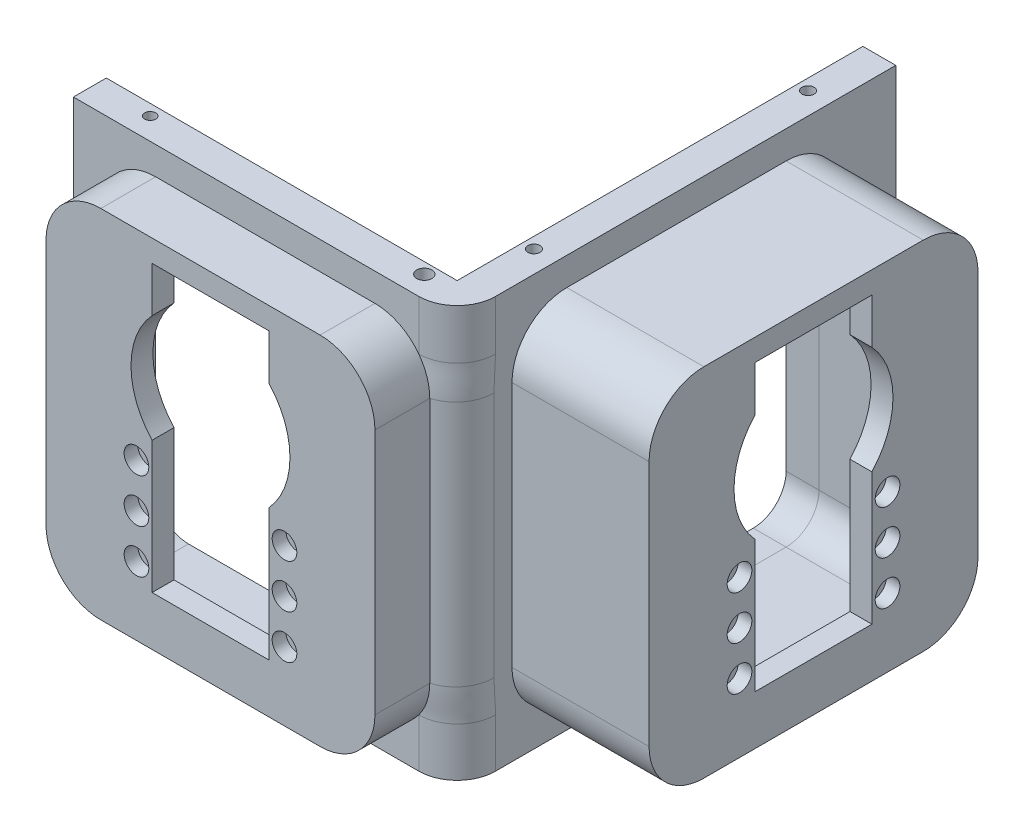
SolidWorks part; units mm, degrees
ref_plane "Front Plane" through (0, 0, 0) normal (0, 0, 1) x (1, 0, 0)
ref_plane "Top Plane" through (0, 0, 0) normal (0, 1, 0) x (1, 0, 0)
ref_plane "Right Plane" through (0, 0, 0) normal (1, 0, 0) x (0, 0, -1)
sketch "Sketch1" plane through (0, 0, 0) normal (0, 0, 1) x (1, 0, 0)
  line L1 (-20, -32.5) -> (20, -32.5)
  line L2 (-30, -22.5) -> (-30, 22.5)
  line L3 (-20, 32.5) -> (20, 32.5)
  line L4 (30, -22.5) -> (30, 22.5)
  line L5 (-30, -32.5) -> (30, 32.5) construction
  line L6 (-30, 32.5) -> (30, -32.5) construction
  arc A1 (20, 32.5) -> (30, 22.5) centre (20, 22.5) cw
  arc A2 (20, -32.5) -> (30, -22.5) centre (20, -22.5) ccw
  arc A3 (-20, -32.5) -> (-30, -22.5) centre (-20, -22.5) cw
  arc A4 (-30, 22.5) -> (-20, 32.5) centre (-20, 22.5) cw
  point P0 (0, 0)
  dimension "D1" = 60
  dimension "D3" = 10
  dimension "D2" = 65
extrude "Boss-Extrude1" add sketch "Sketch1" against normal blind 10
ref_plane "Plane1" through (60, 0, 0) normal (1, 0, 0) x (0, 0, -1)
ref_plane "Plane2" through (60, 0, 0) normal (1, 0, 0) x (0, 0, -1)
sketch "Sketch10" plane through (0, 0, -10) normal (0, 0, -1) x (-1, 0, 0)
  line L0 (0, 0.1039) -> (0, 0) construction
  line L1 (-35, -37.3961) -> (35, -37.3961)
  line L2 (-35, -37.3961) -> (-35, 37.6039)
  line L3 (-35, 37.6039) -> (35, 37.6039)
  line L4 (35, -37.3961) -> (35, 37.6039)
  line L5 (-35, -37.3961) -> (35, 37.6039) construction
  line L6 (-35, 37.6039) -> (35, -37.3961) construction
  point P0 (0, 0.1039)
  point P5 (0, 0.0519)
  dimension "D1" = 75
  dimension "D2" = 70
extrude "Boss-Extrude6" add sketch "Sketch10" along normal blind 80
sketch "Sketch2" plane through (60, 0, 0) normal (1, 0, 0) x (0, 0, -1)
  line L2 (0, 0) -> (146.6861, 0) construction
  line L3 (50, 0) -> (50, 30) construction
  line L5 (10, 37.6039) -> (10, -37.3961) construction
  line L6 (90, 37.6039) -> (90, -37.3961) construction
  line L7 (30, -32.5) -> (70, -32.5)
  line L8 (20, -22.5) -> (20, 22.5)
  line L9 (30, 32.5) -> (70, 32.5)
  line L10 (80, -22.5) -> (80, 22.5)
  line L11 (20, -32.5) -> (80, 32.5) construction
  line L12 (20, 32.5) -> (80, -32.5) construction
  arc A1 (30, -32.5) -> (20, -22.5) centre (30, -22.5) cw
  arc A2 (70, -32.5) -> (80, -22.5) centre (70, -22.5) ccw
  arc A3 (70, 32.5) -> (80, 22.5) centre (70, 22.5) cw
  arc A4 (20, 22.5) -> (30, 32.5) centre (30, 22.5) cw
  dimension "D1" = 60
  dimension "D3" = 10
  dimension "D2" = 65
extrude "Boss-Extrude2" add sketch "Sketch2" against normal up to surface (25 mm away) separate body up to face at (35, 0.1039, -50)
sketch "Sketch11" plane through (0, 37.6039, 0) normal (0, 1, 0) x (1, 0, 0)
  line L1 (-35, 90) -> (29, 90)
  line L2 (-35, 90) -> (-35, 16)
  line L3 (-35, 16) -> (29, 16)
  line L4 (29, 90) -> (29, 16)
  dimension "D1" = 74
  dimension "D2" = 64
extrude "Cut-Extrude5" cut sketch "Sketch11" against normal through all
sketch "Sketch4" plane through (35, 0, 0) normal (-1, 0, 0) x (0, 0, 1)
  line L8 (-70, -28.5) -> (-30, -28.5)
  line L9 (-76, 22.5) -> (-76, -22.5)
  line L10 (-30, 28.5) -> (-70, 28.5)
  line L11 (-24, -22.5) -> (-24, 22.5)
  line L12 (-70, -28.5) -> (-30, -28.5)
  line L13 (-76, 22.5) -> (-76, -22.5)
  line L14 (-30, 28.5) -> (-70, 28.5)
  line L15 (-24, -22.5) -> (-24, 22.5)
  arc A10 (-76, -22.5) -> (-70, -28.5) centre (-70, -22.5) ccw
  arc A11 (-70, 28.5) -> (-76, 22.5) centre (-70, 22.5) ccw
  arc A12 (-24, 22.5) -> (-30, 28.5) centre (-30, 22.5) ccw
  arc A13 (-30, -28.5) -> (-24, -22.5) centre (-30, -22.5) ccw
  arc A14 (-76, -22.5) -> (-70, -28.5) centre (-70, -22.5) ccw
  arc A15 (-70, 28.5) -> (-76, 22.5) centre (-70, 22.5) ccw
  arc A16 (-24, 22.5) -> (-30, 28.5) centre (-30, 22.5) ccw
  arc A17 (-30, -28.5) -> (-24, -22.5) centre (-30, -22.5) ccw
  dimension "D1" = 4
extrude "Cut-Extrude2" cut sketch "Sketch4" against normal through all contours L12 A17 L15 A16 L14 A15 L13 A14 region at (35, 0, -50)
sketch "Sketch5" plane through (60, 0, 0) normal (1, 0, 0) x (0, 0, -1)
  line L0 (50, 0) -> (50, -28.5) construction
  line L1 (30, 28.5) -> (39.35, 28.5)
  line L2 (39.35, 28.5) -> (39.35, -23.5)
  line L3 (39.35, -23.5) -> (60.65, -23.5)
  line L4 (60.65, -23.5) -> (60.65, 28.5)
  line L5 (60.65, 28.5) -> (70, 28.5)
  line L10 (50, 0) -> (63.5, 0) construction
  line L11 (63.5, 0) -> (63.5, -4) construction
  line L12 (63.5, -4) -> (63.5, -12) construction
  line L13 (63.5, -12) -> (63.5, -20) construction
  line L14 (70, -28.5) -> (30, -28.5) construction
  line L15 (30, -28.5) -> (70, -28.5)
  line L18 (30, 28.5) -> (70, 28.5) construction
  line L19 (24, -22.5) -> (24, 22.5) construction
  line L20 (76, 22.5) -> (76, -22.5) construction
  line L21 (24, -22.5) -> (24, 22.5)
  line L22 (76, 22.5) -> (76, -22.5)
  circle A0 centre (50, 0) radius 11 construction
  circle A2 centre (63.5, -4) radius 1.25
  arc A3 (24, -22.5) -> (30, -28.5) centre (30, -22.5) ccw
  circle A5 centre (63.5, -12) radius 1.25
  circle A6 centre (63.5, -20) radius 1.25
  circle A7 centre (36.5, -4) radius 1.25
  circle A8 centre (36.5, -12) radius 1.25
  circle A9 centre (36.5, -20) radius 1.25
  arc A10 (70, -28.5) -> (76, -22.5) centre (70, -22.5) ccw
  arc A11 (76, 22.5) -> (70, 28.5) centre (70, 22.5) ccw construction
  arc A12 (30, 28.5) -> (24, 22.5) centre (30, 22.5) ccw construction
  arc A13 (76, 22.5) -> (70, 28.5) centre (70, 22.5) ccw
  arc A14 (30, 28.5) -> (24, 22.5) centre (30, 22.5) ccw
  point P0 (30, 28.5)
  point P8 (50, -23.5)
  point P14 (50, -28.5)
  dimension "D1" = 22
  dimension "D6" = 2.5
  dimension "D3" = 21.3
  dimension "D4" = 13.5
  dimension "D5" = 4
  dimension "D7" = 8
  dimension "D8" = 8
  dimension "D10" = 5
extrude "Boss-Extrude3" add sketch "Sketch5" against normal blind 4
sketch "Sketch13" plane through (35, 0, 0) normal (1, 0, 0) x (0, 0, -1)
  line L4 (24, 22.5) -> (24, -22.5)
  line L5 (30, -28.5) -> (70, -28.5)
  line L6 (76, -22.5) -> (76, 22.5)
  line L7 (70, 28.5) -> (30, 28.5)
  line L8 (24, 22.5) -> (24, -22.5)
  line L9 (30, -28.5) -> (70, -28.5)
  line L10 (76, -22.5) -> (76, 22.5)
  line L11 (70, 28.5) -> (30, 28.5)
  arc A6 (30, 28.5) -> (24, 22.5) centre (30, 22.5) ccw
  arc A7 (24, -22.5) -> (30, -28.5) centre (30, -22.5) ccw
  arc A8 (70, -28.5) -> (76, -22.5) centre (70, -22.5) ccw
  arc A9 (76, 22.5) -> (70, 28.5) centre (70, 22.5) ccw
  arc A10 (30, 28.5) -> (24, 22.5) centre (30, 22.5) ccw
  arc A11 (24, -22.5) -> (30, -28.5) centre (30, -22.5) ccw
  arc A12 (70, -28.5) -> (76, -22.5) centre (70, -22.5) ccw
  arc A13 (76, 22.5) -> (70, 28.5) centre (70, 22.5) ccw
  dimension "D1" = 0
extrude "Cut-Extrude6" cut sketch "Sketch13" against normal up to surface (6 mm away) up to face at (29, 0.1039, -53)
sketch "Sketch14" plane through (0, 0, 0) normal (0, 0, 1) x (1, 0, 0)
  line L8 (20, 28.5) -> (-20, 28.5)
  line L9 (26, -22.5) -> (26, 22.5)
  line L10 (-20, -28.5) -> (20, -28.5)
  line L11 (-26, 22.5) -> (-26, -22.5)
  line L12 (20, 28.5) -> (-20, 28.5)
  line L13 (26, -22.5) -> (26, 22.5)
  line L14 (-20, -28.5) -> (20, -28.5)
  line L15 (-26, 22.5) -> (-26, -22.5)
  arc A10 (26, 22.5) -> (20, 28.5) centre (20, 22.5) ccw
  arc A11 (20, -28.5) -> (26, -22.5) centre (20, -22.5) ccw
  arc A12 (-26, -22.5) -> (-20, -28.5) centre (-20, -22.5) ccw
  arc A13 (-20, 28.5) -> (-26, 22.5) centre (-20, 22.5) ccw
  arc A14 (26, 22.5) -> (20, 28.5) centre (20, 22.5) ccw
  arc A15 (20, -28.5) -> (26, -22.5) centre (20, -22.5) ccw
  arc A16 (-26, -22.5) -> (-20, -28.5) centre (-20, -22.5) ccw
  arc A17 (-20, 28.5) -> (-26, 22.5) centre (-20, 22.5) ccw
  dimension "D1" = 4
extrude "Cut-Extrude7" cut sketch "Sketch14" against normal up to surface (16 mm away) up to face at (-3, 0.1039, -16)
sketch "Sketch15" plane through (0, 0, 0) normal (0, 0, 1) x (1, 0, 0)
  line L0 (0, 0) -> (0, -17.9719) construction
  line L1 (-20, 28.5) -> (-10.65, 28.5)
  line L2 (-10.65, 28.5) -> (-10.65, -23.5)
  line L3 (-10.65, -23.5) -> (10.65, -23.5)
  line L4 (10.65, -23.5) -> (10.65, 28.5)
  line L5 (10.65, 28.5) -> (20, 28.5)
  line L10 (0, 0) -> (13.5, 0) construction
  line L11 (13.5, 0) -> (13.5, -4) construction
  line L12 (13.5, -4) -> (13.5, -12) construction
  line L13 (13.5, -12) -> (13.5, -20) construction
  line L14 (-20, -28.5) -> (20, -28.5) construction
  line L15 (-20, -28.5) -> (20, -28.5)
  line L18 (20, 28.5) -> (-20, 28.5) construction
  line L19 (26, -22.5) -> (26, 22.5) construction
  line L20 (-26, 22.5) -> (-26, -22.5) construction
  line L21 (26, -22.5) -> (26, 22.5)
  line L22 (-26, 22.5) -> (-26, -22.5)
  circle A0 centre (0, 0) radius 11 construction
  circle A1 centre (13.5, -4) radius 1.25
  circle A3 centre (13.5, -12) radius 1.25
  circle A4 centre (13.5, -20) radius 1.25
  circle A5 centre (-13.5, -4) radius 1.25
  circle A6 centre (-13.5, -12) radius 1.25
  circle A7 centre (-13.5, -20) radius 1.25
  arc A8 (-20, 28.5) -> (-26, 22.5) centre (-20, 22.5) ccw construction
  arc A9 (-26, -22.5) -> (-20, -28.5) centre (-20, -22.5) ccw
  arc A10 (26, -22.5) -> (20, -28.5) centre (20, -22.5) cw
  arc A11 (26, 22.5) -> (20, 28.5) centre (20, 22.5) ccw construction
  arc A12 (-20, 28.5) -> (-26, 22.5) centre (-20, 22.5) ccw
  arc A13 (26, 22.5) -> (20, 28.5) centre (20, 22.5) ccw
  point P5 (0, -23.5)
  point P28 (-19.8602, 28.5)
  dimension "D1" = 22
  dimension "D5" = 2.5
  dimension "D2" = 21.3
  dimension "D3" = 13.5
  dimension "D4" = 4
  dimension "D6" = 8
  dimension "D7" = 8
  dimension "D9" = 5
extrude "Boss-Extrude7" add sketch "Sketch15" against normal blind 4
sketch "Sketch16" plane through (60, 0, 0) normal (1, 0, 0) x (0, 0, -1)
  circle A0 centre (63.5, -4) radius 2.25
  circle A1 centre (63.5, -12) radius 2.25
  circle A2 centre (63.5, -20) radius 2.25
  circle A3 centre (36.5, -20) radius 2.25
  circle A4 centre (36.5, -12) radius 2.25
  circle A5 centre (36.5, -4) radius 2.25
  dimension "D1" = 4.5
extrude "Cut-Extrude8" cut sketch "Sketch16" against normal blind 2.5
fillet "Fillet1" radius 7 1 edges at (35, 0.1039, -10)
fillet "Fillet2" [suppressed] radius 10
sketch "Sketch17" plane through (0, 0, 0) normal (0, 0, 1) x (1, 0, 0)
  circle A0 centre (-13.5, -4) radius 2.25
  circle A1 centre (-13.5, -12) radius 2.25
  circle A2 centre (-13.5, -20) radius 2.25
  circle A3 centre (13.5, -4) radius 2.25
  circle A4 centre (13.5, -12) radius 2.25
  circle A5 centre (13.5, -20) radius 2.25
  dimension "D1" = 4.5
extrude "Cut-Extrude9" cut sketch "Sketch17" against normal blind 2.5
sketch "Sketch18" plane through (0, 0, -16) normal (0, 0, -1) x (-1, 0, 0)
  line L0 (35, 37.6039) -> (-29, 37.6039) construction
  line L1 (-27, 33.6039) -> (-23, 33.6039)
  line L2 (-27, 33.6039) -> (-27, 31.6039)
  line L3 (-27, 31.6039) -> (-23, 31.6039)
  line L4 (-23, 33.6039) -> (-23, 31.6039)
  line L5 (23, 33.6039) -> (27, 33.6039)
  line L6 (23, 33.6039) -> (23, 31.6039)
  line L7 (23, 31.6039) -> (27, 31.6039)
  line L8 (27, 33.6039) -> (27, 31.6039)
  line L9 (-27, -31.3961) -> (-23, -31.3961)
  line L10 (-27, -31.3961) -> (-27, -33.3961)
  line L11 (-27, -33.3961) -> (-23, -33.3961)
  line L12 (-23, -31.3961) -> (-23, -33.3961)
  line L13 (23, -31.3961) -> (27, -31.3961)
  line L14 (23, -31.3961) -> (23, -33.3961)
  line L15 (23, -33.3961) -> (27, -33.3961)
  line L16 (27, -31.3961) -> (27, -33.3961)
  line L17 (35, -37.3961) -> (-29, -37.3961) construction
  line L18 (-23, 31.6039) -> (23, 31.6039) construction
  line L19 (0, 0) -> (0, 37.6039) construction
  point P23 (0, 31.6039)
  point P24 (-25, 33.6039)
  dimension "D1" = 4
  dimension "D2" = 6
  dimension "D3" = 6
  dimension "D4" = 2
  dimension "D5" = 25
extrude "Cut-Extrude10" cut sketch "Sketch18" against normal blind 4
sketch "Sketch19" plane through (29, 0, 0) normal (-1, 0, 0) x (0, 0, 1)
  line L0 (-80, 33.6039) -> (-76, 33.6039)
  line L1 (-80, 33.6039) -> (-80, 31.6039)
  line L2 (-80, 31.6039) -> (-76, 31.6039)
  line L3 (-76, 33.6039) -> (-76, 31.6039)
  line L4 (-30, 33.6039) -> (-26, 33.6039)
  line L5 (-30, 33.6039) -> (-30, 31.6039)
  line L6 (-30, 31.6039) -> (-26, 31.6039)
  line L7 (-26, 33.6039) -> (-26, 31.6039)
  line L8 (-80, -31.3961) -> (-76, -31.3961)
  line L9 (-80, -31.3961) -> (-80, -33.3961)
  line L10 (-80, -33.3961) -> (-76, -33.3961)
  line L11 (-76, -31.3961) -> (-76, -33.3961)
  line L12 (-30, -31.3961) -> (-26, -31.3961)
  line L13 (-30, -31.3961) -> (-30, -33.3961)
  line L14 (-30, -33.3961) -> (-26, -33.3961)
  line L15 (-26, -31.3961) -> (-26, -33.3961)
  line L16 (-76, 31.6039) -> (-30, 31.6039) construction
  line L17 (-53, -20.9793) -> (-53, 16.0207) construction
  line L18 (-53, -37.3961) -> (-53, 37.6039) construction
  line L19 (-16, -37.3961) -> (-90, -37.3961) construction
  line L20 (-16, 37.6039) -> (-90, 37.6039) construction
  point P18 (-53, 31.6039)
  point P19 (-78, 33.6039)
  dimension "D1" = 4
  dimension "D2" = 2
  dimension "D3" = 25
  dimension "D4" = 6
  dimension "D5" = 6
extrude "Cut-Extrude11" cut sketch "Sketch19" against normal blind 4
sketch "Sketch20" plane through (0, 31.6039, 0) normal (0, 1, 0) x (1, 0, 0)
  line L0 (-23, 16) -> (-27, 12) construction
  line L1 (27, 16) -> (23, 12) construction
  circle A0 centre (-25, 14) radius 1
  circle A1 centre (25, 14) radius 1.3784
  dimension "D1" = 2
extrude "Cut-Extrude12" cut sketch "Sketch20" along normal through all
sketch "Sketch21" plane through (0, 31.6039, 0) normal (0, 1, 0) x (1, 0, 0)
  line L0 (33, 30) -> (29, 26) construction
  line L1 (33, 80) -> (29, 76) construction
  circle A0 centre (31, 28) radius 1.1
  circle A1 centre (31, 78) radius 1.1
  dimension "D1" = 2.2
extrude "Cut-Extrude13" cut sketch "Sketch21" along normal through all
ref_plane "Plane3" through (0, 0.1039, 0) normal (0, -1, 0) x (-1, 0, 0)
mirror "Mirror1" about plane through (0, 0.1039, 0) normal (0, -1, 0) of "Cut-Extrude12", "Cut-Extrude13"
sketch "Sketch22" plane through (60, 1.9186, 0) normal (1, 0, 0) x (0, 0, -1)
  line L1 (60.65, -25.4186) -> (39.35, -25.4186) construction
  circle A0 centre (49.9944, 8.4814) radius 14.5
  point P4 (49.9944, 8.494)
  dimension "D1" = 29
  dimension "D2" = 33.9
extrude "Cut-Extrude14" cut sketch "Sketch22" against normal up to surface (4 mm away) up to face at (56, -20, -35.25)
sketch "Sketch23" plane through (0, 0, 0) normal (0, 0, 1) x (1, 0, 0)
  line L0 (10.65, -23.5) -> (-10.65, -23.5) construction
  circle A0 centre (0, 10.4) radius 14.5
  dimension "D1" = 29
  dimension "D2" = 33.9
extrude "Cut-Extrude15" cut sketch "Sketch23" against normal up to surface (4 mm away) up to face at (-14.75, -20, -4)
